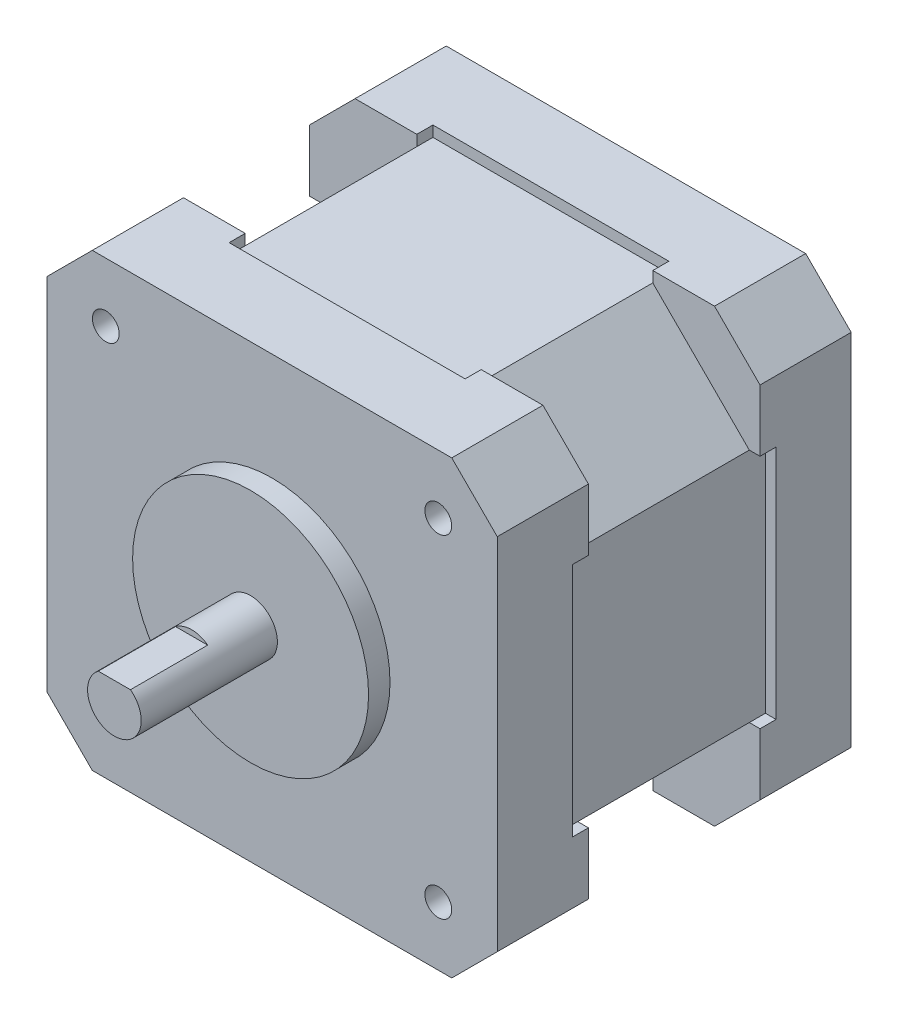
SolidWorks part; units mm, degrees
ref_plane "Front Plane" through (0, 0, 0) normal (0, 0, 1) x (1, 0, 0)
ref_plane "Top Plane" through (0, 0, 0) normal (0, 1, 0) x (1, 0, 0)
ref_plane "Right Plane" through (0, 0, 0) normal (1, 0, 0) x (0, 0, -1)
sketch "Sketch1" plane through (0, 0, 0) normal (0, 0, 1) x (1, 0, 0)
  line L0 (-16.7574, 21) -> (-21, 16.7574)
  line L1 (21, -21) -> (-21, -21)
  line L2 (21, -21) -> (21, 21)
  line L3 (21, 21) -> (-21, 21)
  line L4 (-21, -21) -> (-21, 21)
  line L5 (21, -21) -> (-21, 21) construction
  line L6 (21, 21) -> (-21, -21) construction
  line L7 (0, 0) -> (0, 21) construction
  line L8 (0, 0) -> (21, 0) construction
  line L9 (16.7574, 21) -> (21, 16.7574)
  line L10 (-16.7574, -21) -> (-21, -16.7574)
  line L11 (16.7574, -21) -> (21, -16.7574)
  point P0 (0, 0)
  dimension "D1" = 3
  dimension "Overall Width" = 42
extrude "Boss-Extrude1" add sketch "Sketch1" against normal blind 33 contours L1 L11 L2 L9 L3 L0 L4 L10 region at (0, 0, 0)
hole_wizard "M3x0.5 Tapped Hole1" positions "Sketch3" profile "Sketch2" tap size "M3x0.5" standard "ANSI Metric"
sketch "Sketch3" plane through (0, 0, 0) normal (0, 0, 1) x (1, 0, 0)
  line L1 (15.5, -15.5) -> (-15.5, -15.5) construction
  line L2 (15.5, -15.5) -> (15.5, 15.5) construction
  line L3 (15.5, 15.5) -> (-15.5, 15.5) construction
  line L4 (-15.5, -15.5) -> (-15.5, 15.5) construction
  line L5 (15.5, -15.5) -> (-15.5, 15.5) construction
  line L6 (15.5, 15.5) -> (-15.5, -15.5) construction
  point P2 (-15.5, 15.5)
  point P101 (15.5, -15.5)
  point P102 (15.5, 15.5)
  point P103 (-15.5, -15.5)
  dimension "Hole distance" = 31
sketch "Sketch2" plane through (-15.5, 15.5, 0) normal (1, 0, 0) x (0, -1, 0)
  line L0 (0, 0) -> (0, 8.2511)
  line L1 (0, 8.2511) -> (1.25, 7.5)
  line L2 (1.25, 7.5) -> (1.25, 0)
  line L5 (1.25, 0) -> (0, 0)
  line L10 (0, 8.2511) -> (-1.25, 7.5) construction
  line L11 (0, -6.35) -> (0, 107.95) construction
  dimension "Tap Drill Dia." = 2.5
  dimension "Tap Drill Depth" = 7.5
  dimension "Drill Angle" = 118
ref_plane "Plane1" through (0, 0, -16.5) normal (0, 0, 1) x (1, 0, 0)
sketch "Sketch4" plane through (0, 0, -16.5) normal (0, 0, 1) x (1, 0, 0)
  line L0 (-15.5, 15.5) -> (15.5, -15.5) construction
  line L1 (-15.5, -15.5) -> (15.5, 15.5) construction
  line L2 (16.7574, 21) -> (-16.7574, 21) construction
  line L5 (11, -20) -> (-11, -20)
  line L6 (20, -11) -> (20, 11)
  line L8 (11, 20) -> (-11, 20)
  line L9 (-20, -11) -> (-20, 11)
  line L10 (20, -20) -> (-20, 20) construction
  line L11 (20, 20) -> (-20, -20) construction
  line L13 (-20, 11) -> (-11, 20)
  line L14 (0, 0) -> (0, 17.2431) construction
  line L15 (0, 0) -> (12.072, 0) construction
  line L16 (20, 11) -> (11, 20)
  line L17 (-20, -11) -> (-11, -20)
  line L18 (20, -11) -> (11, -20)
  point P8 (0, 0)
  dimension "D1" = 1
extrude "Cut-Extrude1" cut sketch "Sketch4" against normal mid plane 16 flip side to cut
sketch "Sketch5" plane through (21, 0, 0) normal (1, 0, 0) x (0, 0, -1)
  line L0 (16.5, 23.1) -> (16.5, -23.1) construction
  line L1 (26, -11) -> (7, -11)
  line L2 (26, -11) -> (26, 11)
  line L3 (26, 11) -> (7, 11)
  line L4 (7, -11) -> (7, 11)
  line L5 (26, -11) -> (7, 11) construction
  line L6 (26, 11) -> (7, -11) construction
  line L10 (24.5, 11) -> (8.5, 11) construction
  line L11 (8.5, 16.7574) -> (8.5, -16.7574) construction
  line L12 (24.5, -11) -> (8.5, -11) construction
  point P0 (16.5, 0)
  dimension "D1" = 1.5
extrude "Cut-Extrude2" cut sketch "Sketch5" against normal blind 1
ref_axis "Axis1" through (0, 0, -35.875) along (0, 0, 1)
pattern_circular "CirPattern1" count 4 over 360 about axis through (0, 0, -35.875) along (0, 0, 1) of "Cut-Extrude2"
sketch "Sketch7" plane through (0, 0, 0) normal (0, 0, 1) x (1, 0, 0)
  circle A0 centre (0, 0) radius 11
  dimension "D1" = 22
extrude "Boss-Extrude2" add sketch "Sketch7" along normal blind 2
sketch "Sketch8" plane through (0, 0, 2) normal (0, 0, 1) x (1, 0, 0)
  circle A0 centre (0, 0) radius 2.5
  dimension "D1" = 5
extrude "Boss-Extrude3" add sketch "Sketch8" along normal blind 12.7
sketch "Sketch9" plane through (0, 0, 14.7) normal (0, 0, 1) x (1, 0, 0)
  line L0 (-1.5, 2) -> (1.5, 2)
  circle A0 centre (0, 0) radius 2.5 construction
  circle A3 centre (0, 0) radius 2.5 construction
  arc A4 (1.5, 2) -> (-1.5, 2) centre (0, 0) ccw
  dimension "D shaft profile" = 4.5
extrude "Cut-Extrude3" cut sketch "Sketch9" against normal offset from surface (7.2 mm away) 5.5 up to face at (11, 0, 2)
mirror "Mirror1" about plane through (0, 0, -16.5) normal (0, 0, 1) of "M3x0.5 Tapped Hole1"
